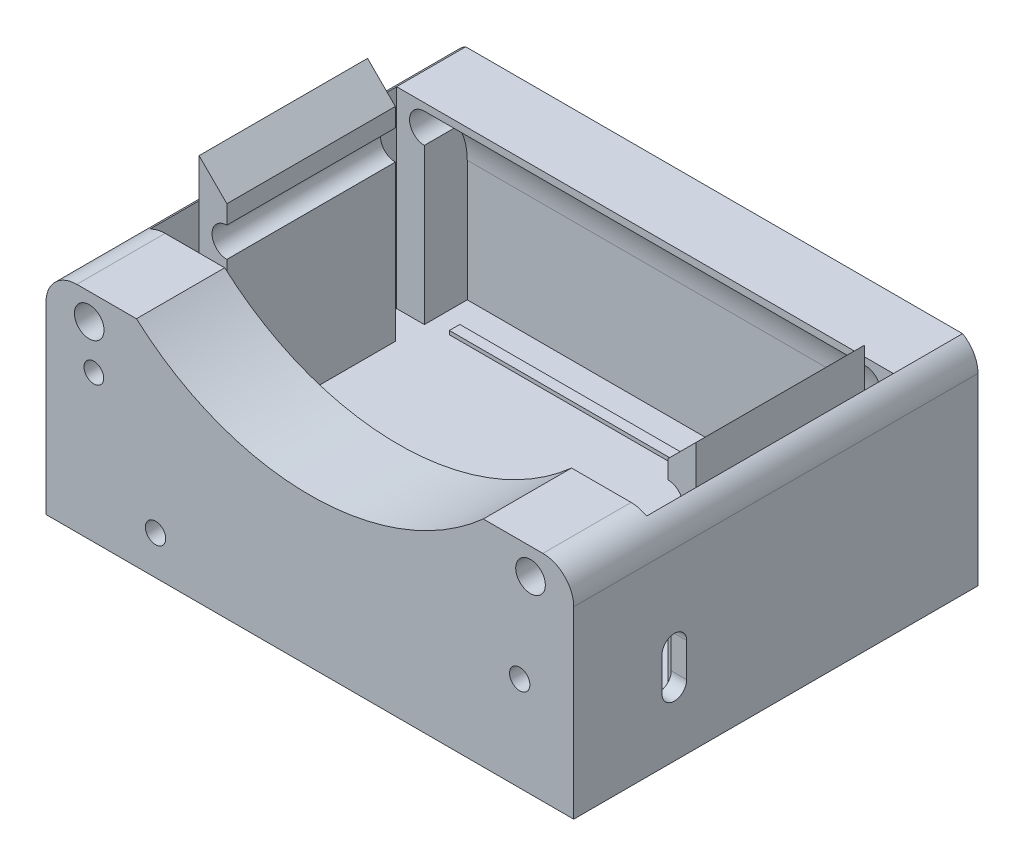
SolidWorks part; units mm, degrees
ref_plane "Front Plane" through (0, 0, 0) normal (0, 0, 1) x (1, 0, 0)
ref_plane "Top Plane" through (0, 0, 0) normal (0, 1, 0) x (1, 0, 0)
ref_plane "Right Plane" through (0, 0, 0) normal (1, 0, 0) x (0, 0, -1)
sketch "Sketch1" plane through (0, 0, 0) normal (0, 0, 1) x (1, 0, 0)
  line L0 (0, -55) -> (0, 55) construction
  line L1 (-37.75, 8.5) -> (-28.0969, 8.5)
  line L2 (-42.75, 3.5) -> (-42.75, -26.3)
  line L3 (-42.75, -26.3) -> (42.75, -26.3)
  line L4 (42.75, 3.5) -> (42.75, -26.3)
  line L5 (55, 0) -> (-55, 0) construction
  line L6 (28.0969, 8.5) -> (37.75, 8.5)
  circle A0 centre (-35.75, 4.25) radius 2.4
  circle A1 centre (35.75, 4.25) radius 2.4
  arc A2 (-28.0969, 8.5) -> (28.0969, 8.5) centre (0, 40) ccw
  arc A3 (37.75, 8.5) -> (42.75, 3.5) centre (37.75, 3.5) cw
  arc A4 (-37.75, 8.5) -> (-42.75, 3.5) centre (-37.75, 3.5) ccw
  circle A5 centre (-25, -20) radius 1.65
  circle A6 centre (34, -11) radius 1.65
  circle A7 centre (-35, -2.5) radius 1.6
  point P16 (42.75, 8.5)
  point P19 (-42.75, 8.5)
  dimension "D5" = 4.8
  dimension "D6" = 4.25
  dimension "D10" = 84.42
  dimension "D12" = 5
  dimension "D13" = 3.3
  dimension "D14" = 3.3
  dimension "D19" = 3.2
  dimension "D1" = 85.5
  dimension "D2" = 42.75
  dimension "D3" = 8.5
  dimension "D4" = 26.3
  dimension "D7" = 7
  dimension "D8" = 4.25
  dimension "D9" = 7
  dimension "D11" = 40
  dimension "D15" = 11
  dimension "D16" = 34
  dimension "D17" = 25
  dimension "D18" = 20
  dimension "D20" = 7.75
  dimension "D21" = 2.5
extrude "Boss-Extrude1" add sketch "Sketch1" along normal blind 8
sketch "Sketch2" plane through (0, 0, 0) normal (0, 0, -1) x (-1, 0, 0)
  line L0 (-40.25, 3.5) -> (-40.25, -23.3)
  line L1 (40.25, -23.3) -> (40.25, 3.5)
  line L2 (-40.25, -23.3) -> (40.25, -23.3)
  line L3 (-42.75, -23.3) -> (42.75, -23.3) construction
  line L4 (-40.25, 3.5) -> (-40.25, -26.3) construction
  line L5 (-42.75, 3.5) -> (-42.75, -26.3)
  line L6 (-42.75, -26.3) -> (42.75, -26.3)
  line L7 (42.75, -26.3) -> (42.75, 3.5)
  line L8 (37.75, 8.5) -> (28.0969, 8.5)
  line L9 (-28.0969, 8.5) -> (-37.75, 8.5)
  line L10 (-42.75, 3.5) -> (-42.75, -26.3)
  line L11 (-42.75, -26.3) -> (42.75, -26.3)
  line L12 (42.75, -26.3) -> (42.75, 3.5)
  line L15 (40.25, -26.3) -> (40.25, 3.5) construction
  line L16 (-40.25, 3.5) -> (-40.25, 7.8301)
  line L17 (40.25, 3.5) -> (40.25, 7.8301)
  arc A3 (42.75, 3.5) -> (37.75, 8.5) centre (37.75, 3.5) ccw
  arc A4 (-28.0969, 8.5) -> (28.0969, 8.5) centre (0, 40) ccw
  arc A5 (-37.75, 8.5) -> (-42.75, 3.5) centre (-37.75, 3.5) ccw
  arc A6 (42.75, 3.5) -> (40.25, 7.8301) centre (37.75, 3.5) ccw
  arc A8 (-40.25, 7.8301) -> (-42.75, 3.5) centre (-37.75, 3.5) ccw
  dimension "D1" = 0
  dimension "D2" = 2.5
  dimension "D3" = 3
extrude "Boss-Extrude2" add sketch "Sketch2" along normal blind 57.5
sketch "Sketch5" plane through (0, 0, 0) normal (0, 0, -1) x (-1, 0, 0)
  line L0 (-38.85, 4.25) -> (-40.25, 4.25)
  line L1 (-40.25, -23.3) -> (-40.25, 7.8301) construction
  line L2 (-40.25, 4.25) -> (-40.25, 7.8301)
  line L3 (-37.75, 8.5) -> (-28.0969, 8.5) construction
  line L4 (-37.75, 8.5) -> (-28.0969, 8.5)
  line L5 (38.85, 4.25) -> (40.25, 4.25)
  line L6 (40.25, 7.8301) -> (40.25, -23.3) construction
  line L7 (40.25, 4.25) -> (40.25, 7.8301)
  line L8 (37.75, 8.5) -> (28.0969, 8.5)
  line L9 (32.65, 4.25) -> (25.1496, 4.25)
  line L10 (22.45, -20) -> (22.45, -23.3)
  line L11 (-32.65, 4.25) -> (-25.1496, 4.25)
  line L12 (40.25, -23.3) -> (-40.25, -23.3) construction
  line L13 (27.55, -20) -> (27.55, -23.3)
  line L14 (40.25, -23.3) -> (-40.25, -23.3) construction
  line L15 (22.45, -23.3) -> (27.55, -23.3)
  arc A0 (-38.85, 4.25) -> (-32.65, 4.25) centre (-35.75, 4.25) ccw
  arc A1 (32.65, 4.25) -> (38.85, 4.25) centre (35.75, 4.25) ccw
  circle A2 centre (-34, -11) radius 2.55
  arc A3 (27.55, -20) -> (22.45, -20) centre (25, -20) ccw
  arc A4 (-28.0969, 8.5) -> (28.0969, 8.5) centre (0, 40) ccw construction
  arc A5 (-37.75, 8.5) -> (-40.25, 7.8301) centre (-37.75, 3.5) ccw construction
  arc A6 (-28.0969, 8.5) -> (28.0969, 8.5) centre (0, 40) ccw
  arc A7 (-37.75, 8.5) -> (-40.25, 7.8301) centre (-37.75, 3.5) ccw
  arc A8 (40.25, 7.8301) -> (37.75, 8.5) centre (37.75, 3.5) ccw construction
  arc A9 (40.25, 7.8301) -> (37.75, 8.5) centre (37.75, 3.5) ccw
  arc A10 (-25.1496, 4.25) -> (25.1496, 4.25) centre (0, 40) ccw
  arc A11 (-29.0953, 7.3806) -> (29.0953, 7.3806) centre (0, 40) ccw construction
  circle A12 centre (35.75, 4.25) radius 2.4 construction
  circle A13 centre (25, -20) radius 1.65 construction
  circle A14 centre (-34, -11) radius 1.65 construction
  circle A15 centre (-35.75, 4.25) radius 2.4 construction
  circle A16 centre (35.75, 4.25) radius 2.4
  circle A17 centre (25, -20) radius 1.65
  circle A18 centre (-34, -11) radius 1.65
  circle A19 centre (-35.75, 4.25) radius 2.4
  dimension "D1" = 6.2
  dimension "D2" = 6.2
  dimension "D3" = 5.1
  dimension "D4" = 5.1
  dimension "D5" = 1.5
extrude "Boss-Extrude5" add sketch "Sketch5" along normal blind 6.3
sketch "Sketch7" plane through (0, -23.3, 0) normal (0, 1, 0) x (1, 0, 0)
  line L0 (-40.25, 14.3) -> (40.25, 14.3) construction
  line L1 (-40.25, 57.5) -> (-40.25, 0) construction
  line L2 (40.25, 57.5) -> (40.25, 0) construction
  line L3 (28.0969, 6.3) -> (-28.0969, 6.3) construction
  line L4 (0, -22.253) -> (0, 22.253) construction
  line L5 (-40.25, 14.3) -> (-27.05, 14.3)
  line L6 (-40.25, 14.3) -> (-40.25, 41.6)
  line L7 (-40.25, 41.6) -> (-27.05, 41.6)
  line L8 (-27.05, 14.3) -> (-27.05, 41.6)
  line L9 (40.25, 41.6) -> (27.05, 41.6)
  line L10 (27.05, 14.3) -> (27.05, 41.6)
  line L11 (40.25, 14.3) -> (27.05, 14.3)
  line L12 (40.25, 14.3) -> (40.25, 41.6)
  dimension "D1" = 8
  dimension "D2" = 13.2
  dimension "D3" = 27.3
extrude "Boss-Extrude6" add sketch "Sketch7" along normal blind 24.26
sketch "Sketch8" plane through (0, 0, -41.6) normal (0, 0, -1) x (-1, 0, 0)
  line L0 (27.05, 0.96) -> (40.25, 0.96) construction
  line L1 (27.05, 0.96) -> (40.25, 0.96)
  line L2 (40.25, 0.96) -> (40.25, 14.16)
  line L3 (40.25, 14.16) -> (27.05, 0.96)
  line L4 (0, 22.253) -> (0, -22.253) construction
  line L5 (-40.25, 0.96) -> (-40.25, 14.16)
  line L6 (-27.05, 0.96) -> (-40.25, 0.96)
  line L7 (-40.25, 14.16) -> (-27.05, 0.96)
extrude "Boss-Extrude7" add sketch "Sketch8" against normal up to surface (27.3 mm away) up to face at (33.65, -11.17, -14.3)
sketch "Sketch9" plane through (0, -23.3, 0) normal (0, 1, 0) x (1, 0, 0)
  line L0 (-40.25, 57.5) -> (40.25, 57.5) construction
  line L1 (-35.75, 57.5) -> (35.75, 57.5)
  line L2 (-35.75, 57.5) -> (-35.75, 6.3)
  line L3 (-35.75, 6.3) -> (35.75, 6.3)
  line L4 (35.75, 57.5) -> (35.75, 6.3)
  line L6 (-40.25, 57.5) -> (-40.25, 41.6) construction
  line L8 (40.25, 57.5) -> (40.25, 41.6) construction
  dimension "D1" = 4.5
  dimension "D2" = 4.5
extrude "Cut-Extrude1" cut sketch "Sketch9" along normal through all
sketch "Sketch11" plane through (-42.75, 0, 0) normal (-1, 0, 0) x (0, 0, 1)
  line L0 (-4.5, -10.65) -> (-4.5, -16.35) construction
  line L1 (-2.7, -10.65) -> (-2.7, -16.35)
  line L2 (-6.3, -10.65) -> (-6.3, -16.35)
  line L5 (33, 0) -> (-33, 0) construction
  line L6 (-6.3, 8.5) -> (-6.3, 7.8301) construction
  arc A0 (-2.7, -10.65) -> (-6.3, -10.65) centre (-4.5, -10.65) ccw
  arc A1 (-6.3, -16.35) -> (-2.7, -16.35) centre (-4.5, -16.35) ccw
  point P2 (-4.5, -13.5)
  dimension "D2" = 1.8
  dimension "D1" = 13.5
  dimension "D3" = 5.7
extrude "Cut-Extrude3" cut sketch "Sketch11" against normal up to surface (2.5 mm away) up to face at (-40.25, -3.74, -6.8667)
sketch "Sketch12" plane through (-42.75, 0, 0) normal (-1, 0, 0) x (0, 0, 1)
  line L0 (-6.3, -10.65) -> (-6.3, -16.35) construction
  line L1 (-6.3, -10.65) -> (-6.3, -16.35)
  line L2 (-2.7, -16.35) -> (-2.7, -10.65) construction
  line L3 (-2.7, -16.35) -> (-2.7, -10.65)
  line L4 (-6.3, -13.5) -> (-2.7, -13.5) construction
  line L5 (-4.5, -16.5) -> (-4.5, -10.5) construction
  line L6 (-8.1, -16.5) -> (-8.1, -10.5)
  line L7 (-0.9, -16.5) -> (-0.9, -10.5)
  arc A0 (-6.3, -16.35) -> (-2.7, -16.35) centre (-4.5, -16.35) ccw construction
  arc A1 (-2.7, -10.65) -> (-6.3, -10.65) centre (-4.5, -10.65) ccw construction
  arc A2 (-6.3, -16.35) -> (-2.7, -16.35) centre (-4.5, -16.35) ccw
  arc A3 (-2.7, -10.65) -> (-6.3, -10.65) centre (-4.5, -10.65) ccw
  arc A4 (-8.1, -16.5) -> (-0.9, -16.5) centre (-4.5, -16.5) ccw
  arc A5 (-0.9, -10.5) -> (-8.1, -10.5) centre (-4.5, -10.5) ccw
  point P10 (-4.5, -13.5)
  dimension "D1" = 3.6
  dimension "D2" = 6
extrude "Cut-Extrude4" cut sketch "Sketch12" against normal blind 2
sketch "Sketch13" plane through (0, -23.3, 0) normal (0, 1, 0) x (1, 0, 0)
  line L0 (0, -22.253) -> (0, 22.253) construction
  line L17 (-32.3, 48.6) -> (32.3, 48.6)
  line L18 (-32.3, 48.6) -> (-32.3, 46.9)
  line L19 (-32.3, 46.9) -> (32.3, 46.9)
  line L20 (32.3, 48.6) -> (32.3, 46.9)
  line L21 (-32.3, 48.6) -> (32.3, 46.9) construction
  line L22 (-32.3, 46.9) -> (32.3, 48.6) construction
  line L24 (-32.3, 15.9) -> (32.3, 15.9)
  line L25 (-32.3, 15.9) -> (-32.3, 14.2)
  line L26 (-32.3, 14.2) -> (32.3, 14.2)
  line L27 (32.3, 15.9) -> (32.3, 14.2)
  line L28 (-32.3, 15.9) -> (32.3, 14.2) construction
  line L29 (-32.3, 14.2) -> (32.3, 15.9) construction
  line L30 (-40.25, 57.5) -> (40.25, 57.5) construction
  point P0 (0, 47.75)
  point P7 (0, 15.05)
  dimension "D1" = 1.7
  dimension "D2" = 64.6
  dimension "D3" = 8.9
  dimension "D4" = 31
extrude "Boss-Extrude8" add sketch "Sketch13" along normal blind 0.6
sketch "Sketch15" plane through (0, -23.3, 0) normal (0, 1, 0) x (1, 0, 0)
  line L0 (28.0969, 6.3) -> (-28.0969, 6.3) construction
  line L1 (-40.25, 57.5) -> (-35.75, 57.5)
  line L2 (-40.25, 57.5) -> (-40.25, 46.3)
  line L3 (-40.25, 46.3) -> (-35.75, 46.3)
  line L4 (-35.75, 53.25) -> (-35.75, 46.3)
  line L5 (-35.75, 41.6) -> (-35.75, 14.3) construction
  line L6 (0, -22.253) -> (0, 22.253) construction
  line L7 (40.25, 46.3) -> (35.75, 46.3)
  line L8 (35.75, 53.25) -> (35.75, 46.3)
  line L9 (40.25, 57.5) -> (35.75, 57.5)
  line L10 (40.25, 57.5) -> (40.25, 46.3)
  line L12 (-35.75, 57.5) -> (35.75, 57.5)
  line L14 (-35.75, 53.25) -> (35.75, 53.25)
  dimension "D1" = 40
  dimension "D2" = 4.25
extrude "Boss-Extrude9" add sketch "Sketch15" along normal up to vertex up to point (-40.25, 7.8301, -41.6)
sketch "Sketch18" plane through (0, 0, 8) normal (0, 0, 1) x (1, 0, 0)
  circle A0 centre (35.75, 4.25) radius 2.4 construction
  circle A1 centre (-35.75, 4.25) radius 2.4 construction
  circle A2 centre (35.75, 4.25) radius 2.4
  circle A3 centre (-35.75, 4.25) radius 2.4
extrude "Cut-Extrude7" cut sketch "Sketch18" against normal up to surface (65.5 mm away) up to face at (0, -4.8783, -57.5)
sketch "Sketch19" plane through (0, 7.8301, 0) normal (0, 1, 0) x (1, 0, 0)
  line L1 (-35.75, 53.25) -> (35.75, 53.25)
  line L2 (-35.75, 53.25) -> (-35.75, 46.3)
  line L3 (-35.75, 46.3) -> (35.75, 46.3)
  line L4 (35.75, 53.25) -> (35.75, 46.3)
extrude "Boss-Extrude11" add sketch "Sketch19" against normal up to vertex up to point (-35.75, 6.65, -46.3)
fillet "Fillet2" radius 11.2 1 edges at (0, 6.65, -53.25)
sketch "Sketch20" plane through (42.75, 0, 0) normal (1, 0, 0) x (0, 0, -1)
  line L0 (8.3, -10.3774) -> (8.3, -15.8774) construction
  line L1 (10.3, -10.3774) -> (10.3, -15.8774)
  line L2 (6.3, -10.3774) -> (6.3, -15.8774)
  line L3 (6.3, 7.8301) -> (6.3, 8.5) construction
  arc A0 (10.3, -10.3774) -> (6.3, -10.3774) centre (8.3, -10.3774) ccw
  arc A1 (6.3, -15.8774) -> (10.3, -15.8774) centre (8.3, -15.8774) ccw
  point P2 (8.3, -13.1274)
  dimension "D1" = 2
  dimension "D2" = 5.5
extrude "Cut-Extrude8" cut sketch "Sketch20" against normal up to surface (2.5 mm away) up to face at (40.25, -3.74, -6.8667)
